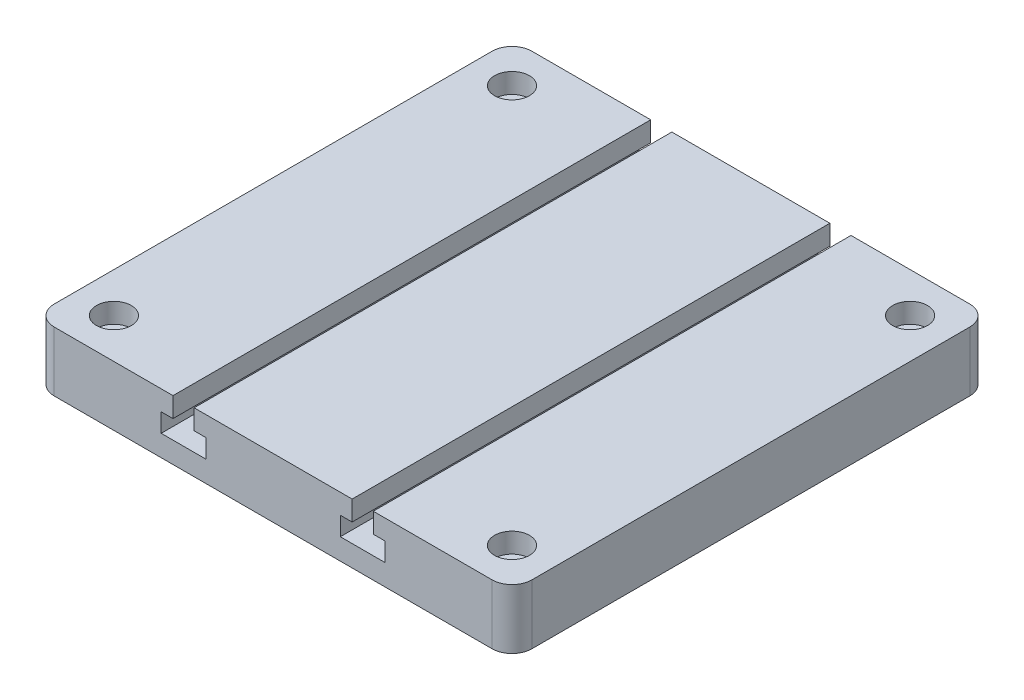
SolidWorks part; units mm, degrees
material "Delrin 2700 NC010, Low Viscosity Acetal Copolymer (SS)"
ref_plane "Front" through (0, 0, 0) normal (0, 0, 1) x (1, 0, 0)
ref_plane "Top" through (0, 0, 0) normal (0, 1, 0) x (1, 0, 0)
ref_plane "Right" through (0, 0, 0) normal (1, 0, 0) x (0, 0, -1)
sketch "Sketch1" plane through (0, 0, 0) normal (0, 1, 0) x (1, 0, 0)
  line L1 (-76.2, 76.2) -> (76.2, 76.2)
  line L2 (-76.2, 76.2) -> (-76.2, -76.2)
  line L3 (-76.2, -76.2) -> (76.2, -76.2)
  line L4 (76.2, 76.2) -> (76.2, -76.2)
  line L5 (-76.2, 76.2) -> (76.2, -76.2) construction
  line L6 (-76.2, -76.2) -> (76.2, 76.2) construction
  point P0 (0, 0)
  dimension "D1" = 152.4
  dimension "D2" = 152.4
extrude "Boss-Extrude1" add sketch "Sketch1" along normal blind 19.05
hole_wizard "CBORE for 1/4 Socket Head Cap Screw1" positions "Sketch2" profile "Sketch3" counterbore size "1/4" standard "ANSI Inch" end condition through all
sketch "Sketch2" plane through (0, 19.05, 0) normal (0, 1, 0) x (1, 0, 0)
  line L1 (-63.5, 63.5) -> (63.5, 63.5) construction
  line L2 (-63.5, 63.5) -> (-63.5, -63.5) construction
  line L3 (-63.5, -63.5) -> (63.5, -63.5) construction
  line L4 (63.5, 63.5) -> (63.5, -63.5) construction
  line L5 (-63.5, 63.5) -> (63.5, -63.5) construction
  line L6 (-63.5, -63.5) -> (63.5, 63.5) construction
  point P0 (-63.5, 63.5)
  point P2 (63.5, 63.5)
  point P4 (63.5, -63.5)
  point P6 (-63.5, -63.5)
  point P108 (0, 0)
  dimension "D1" = 127
  dimension "D2" = 127
sketch "Sketch3" plane through (-63.5, 19.05, -63.5) normal (1, 0, 0) x (0, 0, 1)
  line L0 (0, 0) -> (0, 19.05)
  line L1 (0, 19.05) -> (3.2639, 19.05)
  line L3 (3.2639, 19.05) -> (3.2639, 6.35)
  line L4 (3.2639, 6.35) -> (5.5562, 6.35)
  line L5 (5.5562, 6.35) -> (5.5562, 0)
  line L7 (5.5562, 0) -> (0, 0)
  line L11 (0, -6.35) -> (0, 107.95) construction
  dimension "Thru Hole Dia." = 6.5278
  dimension "Thru Hole Depth" = 19.05
  dimension "C'Bore Dia." = 11.1125
  dimension "C'Bore Depth" = 6.35
sketch "Sketch4" plane through (0, 0, 76.2) normal (0, 0, 1) x (1, 0, 0)
  line L0 (-31.9484, 19.05) -> (-31.9484, 12.7)
  line L1 (-76.2, 19.05) -> (76.2, 19.05) construction
  line L2 (-31.9484, 12.7) -> (-35.7188, 12.7)
  line L3 (-35.7188, 12.7) -> (-35.7188, 6.7469)
  line L4 (-35.7188, 6.7469) -> (-21.4312, 6.7469)
  line L5 (-21.4312, 6.7469) -> (-21.4312, 12.7)
  line L6 (-21.4312, 12.7) -> (-25.2016, 12.7)
  line L7 (-25.2016, 12.7) -> (-25.2016, 19.05)
  line L8 (0, 0) -> (0, 19.05) construction
  line L9 (-28.575, 6.7469) -> (-28.575, 19.05) construction
  line L10 (28.575, 6.7469) -> (28.575, 19.05) construction
  line L11 (25.2016, 12.7) -> (25.2016, 19.05)
  line L12 (21.4312, 12.7) -> (25.2016, 12.7)
  line L13 (21.4312, 6.7469) -> (21.4312, 12.7)
  line L14 (35.7188, 6.7469) -> (21.4312, 6.7469)
  line L15 (35.7188, 12.7) -> (35.7188, 6.7469)
  line L16 (31.9484, 12.7) -> (35.7188, 12.7)
  line L17 (31.9484, 19.05) -> (31.9484, 12.7)
  line L18 (-31.9484, 19.05) -> (-25.2016, 19.05)
  line L19 (25.2016, 19.05) -> (31.9484, 19.05)
  line L20 (-76.2, 0) -> (76.2, 0) construction
  dimension "D1" = 14.2875
  dimension "D2" = 6.7469
  dimension "D3" = 6.35
  dimension "D4" = 57.15
  dimension "D5" = 5.9531
  dimension "D6" = 6.7469
extrude "T-SLOT CUT WITH MCMASTER 8789A16 BIT" cut sketch "Sketch4" against normal through all
fillet "Fillet1" radius 6.35 4 edges at (-76.2, 9.525, 76.2) (76.2, 9.525, 76.2) (76.2, 9.525, -76.2) (-76.2, 9.525, -76.2)
